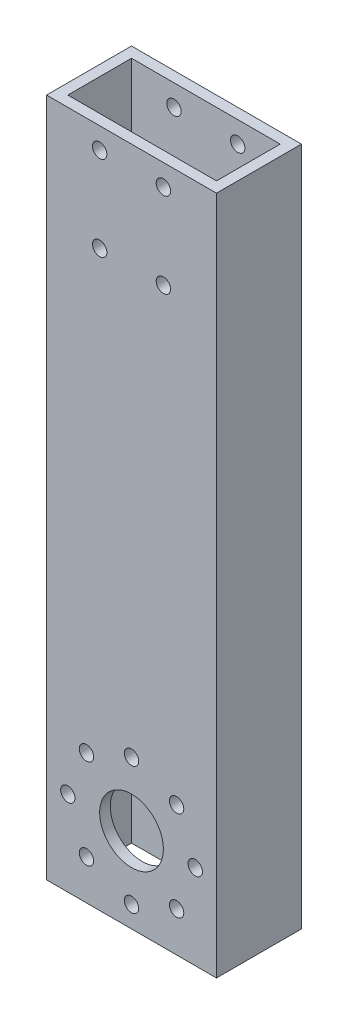
SolidWorks part; units mm, degrees
material "6061-T6 (SS)"
ref_plane "Front Plane" through (0, 0, 0) normal (0, 0, 1) x (1, 0, 0)
ref_plane "Top Plane" through (0, 0, 0) normal (0, 1, 0) x (1, 0, 0)
ref_plane "Right Plane" through (0, 0, 0) normal (1, 0, 0) x (0, 0, -1)
sketch "Sketch2" plane through (0, 0, 0) normal (0, 1, 0) x (1, 0, 0)
  line L1 (-15.1862, -12.028) -> (35.6138, -12.028)
  line L2 (-15.1862, -12.028) -> (-15.1862, 13.372)
  line L3 (-15.1862, 13.372) -> (35.6138, 13.372)
  line L4 (35.6138, -12.028) -> (35.6138, 13.372)
  dimension "D1" = 25.4
  dimension "D2" = 50.8
extrude "Extrude-Thin1" add sketch "Sketch2" along normal blind 457.2 thin thin type one direction reverse wall 3.175
ref_plane "Plane1" through (0, 235.286, -235.286) normal (0, 0.7071, -0.7071) x (-1, 0, 0)
sketch "Sketch8" plane through (0, 235.286, -235.286) normal (0, 0.7071, -0.7071) x (-1, 0, 0)
  line L0 (-35.6138, 313.8338) -> (15.1862, 313.8338) construction
  circle A0 centre (-10.2138, 288.4338) radius 6.35
  point P0 (-10.2138, 288.4338)
  point P3 (-10.2138, 313.8338)
  dimension "D2" = 12.7
  dimension "D1" = 25.4
extrude "Cut-Extrude1" [suppressed] cut sketch "Sketch8" against normal up to surface (63.9513 mm away)
sketch "Sketch9" plane through (-15.1862, 0, 0) normal (-1, 0, 0) x (0, 0, 1)
  line L0 (-13.372, 457.2) -> (12.028, 457.2) construction
  line L1 (-13.372, 457.2) -> (-13.372, 0) construction
  line L2 (2.503, 457.2) -> (-0.672, 520.7) construction
  line L4 (-16.547, 457.2) -> (-3.847, 457.2)
  line L6 (2.503, 457.2) -> (21.553, 457.2)
  line L7 (2.503, 457.2) -> (-3.847, 457.2)
  arc A4 (21.553, 457.2) -> (-16.547, 457.2) centre (2.503, 457.2) ccw
  dimension "D1" = 0
  dimension "D2" = 15.875
extrude "Boss-Extrude5" [suppressed] add sketch "Sketch9" against normal up to surface (3.175 mm away)
sketch "Sketch10" plane through (35.6138, 0, 0) normal (1, 0, 0) x (0, 0, -1)
  line L0 (-12.028, 508) -> (13.372, 508)
  line L12 (13.372, 508) -> (16.547, 508)
  line L13 (-15.203, 508) -> (-12.028, 508)
  arc A2 (16.547, 508) -> (-15.203, 508) centre (0.672, 508) ccw
extrude "Boss-Extrude6" [suppressed] add sketch "Sketch10" against normal up to surface (3.175 mm away)
sketch "Sketch11" [suppressed] plane through (-18.3612, 0, 0) normal (-1, 0, 0) x (0, 0, 1)
  circle A0 centre (-0.672, 508) radius 3.175
  arc A1 (15.203, 508) -> (-16.547, 508) centre (-0.672, 508) ccw construction
  point P6 (-0.672, 523.875)
  dimension "D1" = 6.35
extrude "Cut-Extrude2" [suppressed] cut sketch "Sketch11" against normal up to surface (82.55 mm away)
sketch "Sketch13" plane through (0, 0, 12.028) normal (0, 0, 1) x (1, 0, 0)
  line L0 (-15.1862, 457.2) -> (35.6138, 457.2) construction
  line L1 (-15.1862, 457.2) -> (35.6138, 457.2) construction
  line L3 (35.6138, 457.2) -> (-15.1862, 457.2)
  arc A0 (26.0888, 457.2) -> (-5.6612, 457.2) centre (10.2138, 457.2) ccw construction
  arc A1 (35.6138, 457.2) -> (-15.1862, 457.2) centre (10.2138, 444.8175) ccw
  point P2 (10.2138, 457.2)
  point P7 (35.6138, 457.2)
  point P8 (-15.1862, 457.2)
  point P9 (10.2138, 473.075)
  dimension "D1" = 50.8
  dimension "D2" = 15.875
sketch "Sketch14" plane through (0, 457.2, 0) normal (0, 1, 0) x (1, 0, 0)
  line L1 (32.4388, -8.853) -> (-12.0112, -8.853)
  line L2 (32.4388, -8.853) -> (32.4388, 10.197)
  line L3 (32.4388, 10.197) -> (-12.0112, 10.197)
  line L4 (-12.0112, -8.853) -> (-12.0112, 10.197)
extrude "Extrude-Thin2" [suppressed] add sketch "Sketch14" along normal blind 152.4 thin thin type one direction wall 3.175
sketch "Sketch15" plane through (0, 0, 12.028) normal (0, 0, 1) x (1, 0, 0)
  line L2 (-5.6612, 609.6) -> (26.0888, 609.6)
  line L3 (35.6138, 457.2) -> (-15.1862, 457.2) construction
  arc A1 (26.0888, 609.6) -> (-5.6612, 609.6) centre (10.2138, 609.6) ccw
  dimension "D1" = 31.75
  dimension "D2" = 152.4
extrude "Boss-Extrude7" [suppressed] add sketch "Sketch15" along normal blind 3.175 from offset 22.225
sketch "Sketch17" [suppressed] plane through (0, 0, 15.203) normal (0, 0, 1) x (1, 0, 0)
  line L0 (38.7888, 660.4) -> (38.7888, 584.2)
  line L1 (38.7888, 584.2) -> (38.7888, 508) construction
  line L2 (7.0388, 660.4) -> (7.0388, 584.2)
  line L3 (64.1888, 508) -> (64.1888, 660.4)
  line L4 (64.1888, 660.4) -> (38.7888, 660.4)
  line L5 (-18.3612, 508) -> (-18.3612, 660.4)
  line L6 (-18.3612, 660.4) -> (7.0388, 660.4)
  arc A0 (38.7888, 584.2) -> (64.1888, 508) centre (165.7888, 584.2) ccw
  arc A1 (7.0388, 584.2) -> (-18.3612, 508) centre (-119.9612, 584.2) cw
  dimension "D1" = 76.2
sketch "Sketch18" [suppressed] plane through (0, 0, 40.603) normal (0, 0, 1) x (1, 0, 0)
  line L0 (64.1888, 508) -> (-18.3612, 508) construction
  line L1 (64.1888, 508) -> (-18.3612, 508) construction
  line L2 (38.7888, 660.4) -> (64.1888, 508)
  line L3 (7.0388, 660.4) -> (38.7888, 660.4) construction
  line L4 (7.0388, 660.4) -> (-18.3612, 508)
  line L5 (7.0388, 660.4) -> (38.7888, 660.4)
  line L6 (64.1888, 508) -> (64.1888, 482.6)
  line L7 (64.1888, 482.6) -> (-18.3612, 482.6)
  line L8 (-18.3612, 482.6) -> (-18.3612, 508)
  arc A0 (38.7888, 660.4) -> (7.0388, 660.4) centre (22.9138, 660.4) ccw construction
  dimension "D1" = 25.4
extrude "Boss-Extrude9" [suppressed] add sketch "Sketch18" against normal blind 3.175
sketch "Sketch19" [suppressed] plane through (0, 0, 37.428) normal (0, 0, -1) x (-1, 0, 0)
  line L0 (-64.1888, 508) -> (18.3612, 508)
  line L1 (-64.1888, 508) -> (-64.1888, 482.6)
  line L2 (18.3612, 508) -> (18.3612, 482.6)
  line L3 (-64.1888, 482.6) -> (18.3612, 482.6)
  line L4 (15.1862, 508) -> (-61.0138, 508) construction
  dimension "D1" = 25.4
  dimension "D2" = 82.55
extrude "Boss-Extrude10" [suppressed] add sketch "Sketch19" along normal up to next
sketch "Sketch21" [suppressed] plane through (0, 0, -16.547) normal (0, 0, -1) x (-1, 0, 0)
  line L5 (18.3612, 508) -> (-7.0388, 660.4)
  line L6 (18.3612, 482.6) -> (18.3612, 508)
  line L7 (-64.1888, 482.6) -> (18.3612, 482.6)
  line L8 (-64.1888, 508) -> (-64.1888, 482.6)
  line L9 (-38.7888, 660.4) -> (-64.1888, 508)
  line L10 (18.3612, 508) -> (-7.0388, 660.4)
  line L11 (18.3612, 482.6) -> (18.3612, 508)
  line L12 (-64.1888, 482.6) -> (18.3612, 482.6)
  line L13 (-64.1888, 508) -> (-64.1888, 482.6)
  line L14 (-38.7888, 660.4) -> (-64.1888, 508)
  arc A1 (-7.0388, 660.4) -> (-38.7888, 660.4) centre (-22.9138, 660.4) ccw
  arc A2 (-7.0388, 660.4) -> (-38.7888, 660.4) centre (-22.9138, 660.4) ccw
  dimension "D1" = 0
extrude "Boss-Extrude12" [suppressed] add sketch "Sketch21" along normal blind 3.175 from offset 22.225 separate body
sketch "Sketch22" [suppressed] plane through (0, 0, -38.772) normal (0, 0, 1) x (1, 0, 0)
  line L1 (64.1888, 482.6) -> (-18.3612, 482.6)
  line L2 (64.1888, 482.6) -> (64.1888, 508)
  line L3 (64.1888, 508) -> (-18.3612, 508)
  line L4 (-18.3612, 482.6) -> (-18.3612, 508)
extrude "Boss-Extrude13" [suppressed] add sketch "Sketch22" along normal up to surface (22.225 mm away)
sketch "Sketch16" [suppressed] plane through (0, 0, 15.203) normal (0, 0, 1) x (1, 0, 0)
  arc A0 (38.7888, 660.4) -> (7.0388, 660.4) centre (22.9138, 660.4) ccw construction
  arc A1 (38.7888, 660.4) -> (7.0388, 660.4) centre (22.9138, 660.4) ccw construction
  circle A2 centre (22.9138, 660.4) radius 3.175
  dimension "D1" = 6.35
extrude "Cut-Extrude6" [suppressed] cut sketch "Sketch16" against normal through all both and the other way through all
sketch "Sketch23" plane through (0, 457.2, 0) normal (0, 1, 0) x (1, 0, 0)
  line L1 (91.5301, -40.8812) -> (-34.4515, -40.8812)
  line L2 (91.5301, -40.8812) -> (91.5301, 37.0604)
  line L3 (91.5301, 37.0604) -> (-34.4515, 37.0604)
  line L4 (-34.4515, -40.8812) -> (-34.4515, 37.0604)
sketch "Sketch25" plane through (0, 0, 0) normal (0, -1, 0) x (1, 0, 0)
  line L0 (-12.0112, -10.197) -> (-12.0112, 8.853) construction
  line L1 (32.4388, -10.197) -> (-12.0112, -10.197) construction
  line L2 (-12.0112, 8.853) -> (32.4388, 8.853) construction
  line L3 (32.4388, 8.853) -> (32.4388, -10.197) construction
  line L4 (-15.1862, 12.028) -> (-15.1862, -13.372)
  line L5 (-15.1862, -13.372) -> (35.6138, -13.372)
  line L6 (35.6138, -13.372) -> (35.6138, 12.028)
  line L7 (35.6138, 12.028) -> (-15.1862, 12.028)
  line L8 (-15.1862, 12.028) -> (-15.1862, -13.372)
  line L9 (-15.1862, -13.372) -> (35.6138, -13.372)
  line L10 (35.6138, -13.372) -> (35.6138, 12.028)
  line L11 (35.6138, 12.028) -> (-15.1862, 12.028)
  line L12 (-12.0112, -10.197) -> (-12.0112, 8.853)
  line L13 (32.4388, -10.197) -> (-12.0112, -10.197)
  line L14 (-12.0112, 8.853) -> (32.4388, 8.853)
  line L15 (32.4388, 8.853) -> (32.4388, -10.197)
  dimension "D1" = 0
extrude "Boss-Extrude14" add sketch "Sketch25" along normal blind 25.4
sketch "Sketch28" plane through (0, 0, -13.372) normal (0, 0, -1) x (-1, 0, 0)
  line L0 (9.8842, -20.0979) -> (-30.3117, 20.0979) construction
  line L1 (-35.6138, 457.2) -> (-35.6138, -25.4) construction
  line L2 (15.1862, -25.4) -> (-35.6138, -25.4) construction
  line L3 (9.285, 19.4988) -> (-29.7126, -19.4988) construction
  line L4 (-10.2138, 0) -> (-10.2138, 61.5696) construction
  circle A0 centre (-10.2138, 0) radius 12.7
  circle A1 centre (-10.2138, 0) radius 19.05 construction
  circle A2 centre (-23.6841, -13.4704) radius 2.1527
  circle A3 centre (-29.2638, 0) radius 2.1527
  circle A4 centre (-23.6841, 13.4704) radius 2.1527
  circle A5 centre (-10.2138, 19.05) radius 2.1526
  circle A6 centre (3.2566, 13.4704) radius 2.1526
  circle A7 centre (8.8362, 0) radius 2.1526
  circle A8 centre (3.2566, -13.4704) radius 2.1526
  circle A9 centre (-10.2138, -19.05) radius 2.1526
  point P7 (-29.2638, 0)
  point P8 (-10.2138, 19.05)
  point P9 (8.8362, 0)
  point P10 (-10.2138, -19.05)
  point P11 (3.2566, -13.4704)
  point P15 (-10.2138, 0)
  point P17 (-10.2138, 0)
  point P19 (-23.6841, -13.4704)
  point P20 (-23.6841, 13.4704)
  point P21 (3.2566, 13.4704)
  dimension "D1" = 25.4
  dimension "D3" = 25.4
  dimension "D4" = 38.1
  dimension "D7" = 4.3053
  dimension "D2" = 25.4
  dimension "D5" = 45
  dimension "D6" = 45
extrude "Cut-Extrude9" [suppressed] cut sketch "Sketch28" against normal up to surface (25.4 mm away)
sketch "Sketch29" plane through (0, 457.2, 0) normal (0, 1, 0) x (1, 0, 0)
  line L0 (-12.0112, 10.197) -> (-12.0112, -8.853) construction
  line L1 (-12.0112, -8.853) -> (32.4388, -8.853) construction
  line L2 (32.4388, 10.197) -> (-12.0112, 10.197) construction
  line L3 (32.4388, -8.853) -> (32.4388, 10.197) construction
  line L4 (-15.1862, 13.372) -> (-15.1862, -12.028)
  line L5 (-15.1862, -12.028) -> (35.6138, -12.028)
  line L6 (35.6138, -12.028) -> (35.6138, 13.372)
  line L7 (35.6138, 13.372) -> (-15.1862, 13.372)
  line L8 (-15.1862, 13.372) -> (-15.1862, -12.028)
  line L9 (-15.1862, -12.028) -> (35.6138, -12.028)
  line L10 (35.6138, -12.028) -> (35.6138, 13.372)
  line L11 (35.6138, 13.372) -> (-15.1862, 13.372)
  line L12 (-12.0112, 10.197) -> (-12.0112, -8.853)
  line L13 (-12.0112, -8.853) -> (32.4388, -8.853)
  line L14 (32.4388, 10.197) -> (-12.0112, 10.197)
  line L15 (32.4388, -8.853) -> (32.4388, 10.197)
  dimension "D1" = 0
extrude "Cut-Extrude10" cut sketch "Sketch29" against normal blind 203.2
sketch "Sketch30" [suppressed] plane through (0, 457.2, 0) normal (0, 1, 0) x (1, 0, 0)
  line L4 (-15.1862, 13.372) -> (-15.1862, -12.028)
  line L5 (-15.1862, -12.028) -> (35.6138, -12.028)
  line L6 (35.6138, -12.028) -> (35.6138, 13.372)
  line L7 (35.6138, 13.372) -> (-15.1862, 13.372)
  line L10 (35.6138, -12.028) -> (35.6138, 13.372)
  line L12 (-15.1862, 13.372) -> (-15.1862, -12.028)
  line L13 (-15.1862, -12.028) -> (35.6138, -12.028)
  line L14 (35.6138, -12.028) -> (35.6138, 13.372)
  line L15 (35.6138, 13.372) -> (-15.1862, 13.372)
  dimension "D1" = 0
extrude "Cut-Extrude11" [suppressed] cut sketch "Sketch30" against normal blind 44.45
sketch "Sketch32" [suppressed] plane through (0, 457.2, 0) normal (0, 1, 0) x (1, 0, 0)
  line L1 (55.4573, 34.4048) -> (-49.9988, 34.4048)
  line L2 (55.4573, 34.4048) -> (55.4573, -79.0273)
  line L3 (55.4573, -79.0273) -> (-49.9988, -79.0273)
  line L4 (-49.9988, 34.4048) -> (-49.9988, -79.0273)
extrude "Cut-Extrude13" [suppressed] cut sketch "Sketch32" against normal blind 152.4
sketch "Sketch33" [suppressed] plane through (0, 0, -13.372) normal (0, 0, -1) x (-1, 0, 0)
  line L0 (15.1862, 304.8) -> (-35.6138, 304.8) construction
  line L1 (15.1862, 304.8) -> (-35.6138, 304.8) construction
  line L2 (-10.2138, 304.8) -> (-10.2138, 260.9105) construction
  circle A0 centre (-22.9138, 295.275) radius 2.1526
  circle A2 centre (-22.9138, 276.225) radius 2.1526
  circle A5 centre (2.4862, 295.275) radius 2.1526
  circle A6 centre (2.4862, 276.225) radius 2.1526
  dimension "D1" = 4.3053
  dimension "D2" = 9.525
  dimension "D3" = 19.05
  dimension "D4" = 12.7
extrude "Cut-Extrude14" [suppressed] cut sketch "Sketch33" against normal up to surface (25.4 mm away)
sketch "Sketch34" plane through (0, 0, 12.028) normal (0, 0, 1) x (1, 0, 0)
  line L0 (35.6138, -25.4) -> (-15.1862, -25.4) construction
  line L1 (-15.1862, 254) -> (-15.1862, -25.4) construction
  line L2 (10.2138, 0) -> (58.1998, 0) construction
  line L3 (-29.5569, 39.7707) -> (49.9845, -39.7707) construction
  line L4 (-21.4398, -31.6535) -> (41.8673, 31.6535) construction
  line L5 (10.2138, 0) -> (10.2138, -82.8686) construction
  circle A0 centre (10.2138, 0) radius 9.525
  circle A1 centre (10.2138, 0) radius 19.05 construction
  circle A2 centre (29.2638, 0) radius 2.1527
  circle A3 centre (23.6841, 13.4704) radius 2.1527
  circle A4 centre (10.2138, 19.05) radius 2.1526
  circle A5 centre (-3.2566, 13.4704) radius 2.1526
  circle A6 centre (-8.8362, 0) radius 2.1526
  circle A7 centre (-3.2566, -13.4704) radius 2.1526
  circle A8 centre (10.2138, -19.05) radius 2.1526
  circle A9 centre (23.6841, -13.4704) radius 2.1527
  point P7 (10.2138, 19.05)
  point P13 (10.2138, 0)
  point P16 (10.2138, 0)
  point P18 (-8.8362, 0)
  point P19 (10.2138, -19.05)
  point P20 (29.2638, 0)
  point P21 (23.6841, 13.4704)
  point P22 (-3.2566, 13.4704)
  point P23 (10.2138, -19.05)
  point P24 (23.6841, -13.4704)
  dimension "D1" = 19.05
  dimension "D4" = 38.1
  dimension "D7" = 4.3053
  dimension "D2" = 25.4
  dimension "D3" = 25.4
  dimension "D5" = 45
  dimension "D6" = 45
extrude "Cut-Extrude15" cut sketch "Sketch34" against normal up to surface (25.4 mm away) up to face at (10.2138, 114.3, -13.372)
sketch "Sketch35" plane through (0, 254, 0) normal (0, 1, 0) x (1, 0, 0)
  line L1 (35.6138, 13.372) -> (-15.1862, 13.372)
  line L2 (35.6138, 13.372) -> (35.6138, -12.028)
  line L3 (35.6138, -12.028) -> (-15.1862, -12.028)
  line L4 (-15.1862, 13.372) -> (-15.1862, -12.028)
extrude "Cut-Extrude16" cut sketch "Sketch35" against normal blind 76.2
sketch "Sketch31" plane through (0, 0, -13.372) normal (0, 0, -1) x (-1, 0, 0)
  line L1 (-35.6138, 177.8) -> (-35.6138, -25.4) construction
  line L2 (-35.6138, 177.8) -> (15.1862, 177.8) construction
  circle A0 centre (-19.7388, 146.05) radius 2.1527
  circle A1 centre (-0.6888, 146.05) radius 2.1527
  circle A2 centre (-19.7388, 171.45) radius 2.1527
  circle A3 centre (-0.6888, 171.45) radius 2.1527
  dimension "D1" = 4.3053
  dimension "D2" = 6.35
  dimension "D3" = 25.4
  dimension "D4" = 15.875
  dimension "D5" = 19.05
extrude "Cut-Extrude12" cut sketch "Sketch31" against normal through all both and the other way through all
equation "\"0.625n\"=0.5"
